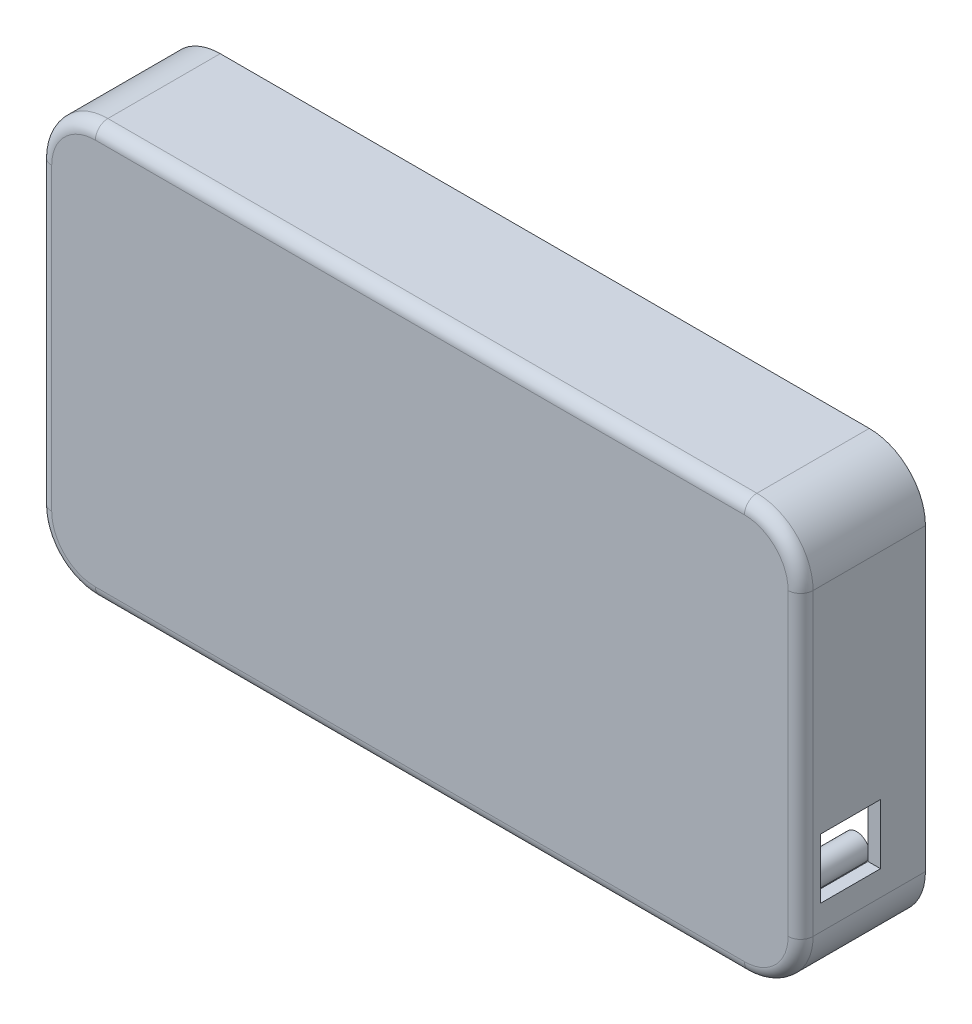
SolidWorks part; units mm, degrees
material "交联聚乙烯"
ref_plane "前视基准面" through (0, 0, 0) normal (0, 0, 1) x (1, 0, 0)
ref_plane "上视基准面" through (0, 0, 0) normal (0, 1, 0) x (1, 0, 0)
ref_plane "右视基准面" through (0, 0, 0) normal (1, 0, 0) x (0, 0, -1)
sketch "草图1" plane through (0, 0, 0) normal (0, 0, 1) x (1, 0, 0)
  line L1 (-130, 82.5) -> (130, 82.5)
  line L2 (-152.5, 60) -> (-152.5, -60)
  line L3 (-130, -82.5) -> (130, -82.5)
  line L4 (152.5, 60) -> (152.5, -60)
  line L5 (0, -82.5) -> (0, 82.5) construction
  line L6 (-152.5, 0) -> (152.5, 0) construction
  line L14 (-130, 77.5) -> (130, 77.5)
  line L15 (147.5, 60) -> (147.5, -60)
  line L16 (-130, -77.5) -> (130, -77.5)
  line L17 (-147.5, 60) -> (-147.5, -60)
  line L18 (-150.2, 60) -> (-150.2, -60)
  line L19 (-130, -80.2) -> (130, -80.2)
  line L20 (150.2, 60) -> (150.2, -60)
  line L21 (-130, 80.2) -> (130, 80.2)
  arc A0 (-130, -82.5) -> (-152.5, -60) centre (-130, -60) cw
  arc A1 (130, -82.5) -> (152.5, -60) centre (130, -60) ccw
  arc A2 (152.5, 60) -> (130, 82.5) centre (130, 60) ccw
  arc A3 (-152.5, 60) -> (-130, 82.5) centre (-130, 60) cw
  arc A12 (147.5, 60) -> (130, 77.5) centre (130, 60) ccw
  arc A13 (130, -77.5) -> (147.5, -60) centre (130, -60) ccw
  arc A14 (-130, -77.5) -> (-147.5, -60) centre (-130, -60) cw
  arc A15 (-147.5, 60) -> (-130, 77.5) centre (-130, 60) cw
  circle A16 centre (130, 60) radius 2.6
  circle A17 centre (130, 60) radius 5.1
  circle A18 centre (130, -60) radius 2.6
  circle A19 centre (130, -60) radius 5.1
  circle A20 centre (-130, 60) radius 2.6
  circle A21 centre (-130, 60) radius 5.1
  circle A22 centre (-130, -60) radius 2.6
  circle A23 centre (-130, -60) radius 5.1
  arc A24 (-130, -80.2) -> (-150.2, -60) centre (-130, -60) cw
  arc A25 (130, -80.2) -> (150.2, -60) centre (130, -60) ccw
  arc A26 (150.2, 60) -> (130, 80.2) centre (130, 60) ccw
  arc A27 (-150.2, 60) -> (-130, 80.2) centre (-130, 60) cw
  point P0 (0, 0)
  point P6 (-152.5, -82.5)
  point P9 (152.5, -82.5)
  point P12 (152.5, 82.5)
  dimension "D3" = 22.5
  dimension "D6" = 5.2
  dimension "D8" = 5.2
  dimension "D10" = 5.2
  dimension "D12" = 5.2
  dimension "D1" = 305
  dimension "D2" = 165
  dimension "D4" = 2.3
  dimension "D7" = 2.5
  dimension "D9" = 2.5
  dimension "D11" = 2.5
  dimension "D13" = 2.5
extrude "凸台-拉伸1" add sketch "草图1" along normal blind 50 contours A0 L2 A3 L1 A2 L4 A1 L3
extrude "切除-拉伸1" cut sketch "草图1<4>" along normal blind 45 contours A15 L17 A14 L16 A13 L15 A12 L14 region at (0, 0, 0)
sketch "草图1<4>" plane through (0, 0, 0) normal (0, 0, 1) x (1, 0, 0) same geometry as "草图1"
sketch "草图3" plane through (0, 0, 0) normal (0, 0, -1) x (-1, 0, 0)
extrude "切除-拉伸2" cut sketch "草图1<5>" along normal blind 5 contours A27 L21 A26 L20 A25 L19 A24 L18 L17 A15 L14 A12 L15 A13 L16 A14 region at (-144.0428, 74.0428, 0)
sketch "草图1<5>" plane through (0, 0, 0) normal (0, 0, 1) x (1, 0, 0) same geometry as "草图1"
extrude "切除-拉伸3" cut sketch "草图1<6>" along normal blind 5 contours A23 | A21 | A17 | A19
sketch "草图1<6>" plane through (0, 0, 0) normal (0, 0, 1) x (1, 0, 0) same geometry as "草图1"
extrude "切除-拉伸4" cut sketch "草图1<7>" along normal blind 25 contours A22 | A16 | A18 | A20 region at (130, 60, 0) region at (130, -60, 0) region at (-130, -60, 0)
sketch "草图1<7>" plane through (0, 0, 0) normal (0, 0, 1) x (1, 0, 0) same geometry as "草图1"
fillet "圆角2" radius 5 4 edges at (0, -82.5, 50) (152.5, 0, 50) (0, 82.5, 50) (-152.5, 0, 50) type face fillet first side face at (0, 0, 50) second side face at (-152.5, 0, 25) second side face at (0, -82.5, 25) second side face at (152.5, 0, 25) second side face at (0, 82.5, 25)
sketch3d "3D草图1"
  point P0 (44.0813, -82.5, 36.7135)
sketch "草图14" plane through (0, -82.5, 0) normal (0, -1, 0) x (1, 0, 0)
  line L0 (-130, 45) -> (130, 45) construction
  line L5 (-80, 38) -> (-71, 38) construction
  line L6 (-130, 45) -> (-130, 0) construction
  line L8 (-87, 33.5) -> (-73, 33.5)
  line L9 (-87, 33.5) -> (-87, 42.5)
  line L10 (-87, 42.5) -> (-73, 42.5)
  line L11 (-73, 33.5) -> (-73, 42.5)
  line L12 (-80, 42.5) -> (-80, 33.5) construction
  line L13 (-87, 38) -> (-73, 38) construction
  line L14 (-87, 33.5) -> (-73, 33.5)
  line L15 (-87, 42.5) -> (-73, 42.5)
  line L16 (0, 45) -> (0, 33.2265) construction
  circle A0 centre (-71, 38) radius 1.6
  circle A2 centre (-89, 38) radius 1.6
  point P0 (-80, 38)
  dimension "D5" = 3.2
  dimension "D1" = 14
  dimension "D2" = 9
  dimension "D3" = 7
  dimension "D4" = 9
  dimension "D6" = 50
extrude "USB口" cut sketch "草图14" against normal blind 5 contours L8 L11 L10 L9 | A2 | A0 region at (-80, -82.5, 38) region at (-89, -82.5, 38)
sketch "草图16" plane through (152.5, 0, 0) normal (1, 0, 0) x (0, 0, -1)
  line L0 (-45, 60) -> (-45, -60) construction
  line L3 (-42, -26) -> (-18, -26)
  line L4 (-42, -26) -> (-42, -50)
  line L5 (-42, -50) -> (-18, -50)
  line L6 (-18, -26) -> (-18, -50)
  line L7 (-30, -50) -> (-30, -26) construction
  line L8 (-42, -38) -> (-18, -38) construction
  line L9 (-45, -60) -> (0, -60) construction
  point P0 (-30, -38)
  dimension "D1" = 24
  dimension "D2" = 24
  dimension "D3" = 10
  dimension "D4" = 15
extrude "切除-拉伸12" cut sketch "草图16" against normal blind 5
sketch "草图18" plane through (-152.5, 0, 0) normal (-1, 0, 0) x (0, 0, 1)
  line L0 (45, -60) -> (45, 60) construction
  line L3 (45, -60) -> (0, -60) construction
  line L4 (18, -26) -> (42, -26)
  line L5 (18, -26) -> (18, -50)
  line L6 (18, -50) -> (42, -50)
  line L7 (42, -26) -> (42, -50)
  line L8 (30, -50) -> (30, -26) construction
  line L9 (18, -38) -> (42, -38) construction
  point P4 (30, -38)
  dimension "D1" = 24
  dimension "D2" = 24
  dimension "D3" = 10
  dimension "D4" = 15
extrude "切除-拉伸13" cut sketch "草图18" against normal blind 5
sketch "草图19" plane through (0, 0, 45) normal (0, 0, -1) x (-1, 0, 0)
  line L0 (-103, 36) -> (-18, 36) construction
  line L1 (-103, 40) -> (-18, 40)
  line L2 (-103, 32) -> (-18, 32)
  line L3 (152.5, 0) -> (-152.5, 0) construction
  line L4 (0, -82.5) -> (0, 82.5) construction
  line L5 (-147.5, 0) -> (-107.2295, 0) construction
  line L6 (0, 77.5) -> (0, 61.8371) construction
  line L7 (103, 36) -> (18, 36) construction
  line L8 (103, 40) -> (18, 40)
  line L9 (103, 32) -> (18, 32)
  line L10 (-103, -24) -> (-23, -24) construction
  line L11 (-103, -20) -> (-23, -20)
  line L12 (-103, -28) -> (-23, -28)
  line L14 (103, -24) -> (23, -24) construction
  line L15 (103, -20) -> (23, -20)
  line L16 (103, -28) -> (23, -28)
  arc A0 (-103, 40) -> (-103, 32) centre (-103, 36) ccw
  arc A1 (-18, 32) -> (-18, 40) centre (-18, 36) ccw
  arc A2 (103, 40) -> (103, 32) centre (103, 36) cw
  arc A3 (18, 32) -> (18, 40) centre (18, 36) cw
  arc A4 (-103, -20) -> (-103, -28) centre (-103, -24) ccw
  arc A5 (-23, -28) -> (-23, -20) centre (-23, -24) ccw
  arc A6 (103, -20) -> (103, -28) centre (103, -24) cw
  arc A7 (23, -28) -> (23, -20) centre (23, -24) cw
  point P2 (-60.5, 36)
  point P13 (60.5, 36)
  point P23 (-63, -24)
  point P33 (63, -24)
  dimension "D2" = 4
  dimension "D7" = 4
  dimension "D8" = 80
  dimension "D1" = 85
  dimension "D3" = 18
  dimension "D4" = 32
  dimension "D5" = 23
  dimension "D6" = 20
extrude "凸台-拉伸2" add sketch "草图19" along normal blind 40
sketch "草图29" plane through (0, 0, 45) normal (0, 0, -1) x (-1, 0, 0)
  line L0 (14.35, -45.2) -> (-14.35, -45.2)
  line L1 (12.85, -43.7) -> (-12.85, -43.7)
  line L2 (12.85, -43.7) -> (12.85, -20)
  line L3 (12.85, -20) -> (-12.85, -20)
  line L4 (-12.85, -43.7) -> (-12.85, -20)
  line L5 (0, -20) -> (0, -43.7) construction
  line L6 (12.85, -31.85) -> (-12.85, -31.85) construction
  line L7 (0, -41.7182) -> (0, 1.1541) construction
  line L8 (-14.35, -45.2) -> (-14.35, -18.5)
  line L9 (14.35, -18.5) -> (-14.35, -18.5)
  line L10 (17.8546, 0) -> (-23.7773, 0) construction
  line L11 (14.35, -45.2) -> (14.35, -18.5)
  line L12 (0, -31.85) -> (-17.5, -31.85) construction
  line L13 (12.85, -20) -> (12.85, -18.5)
  line L14 (-30, 20) -> (30, 20) construction
  line L15 (-30, 20) -> (-30, -10) construction
  line L16 (-30, -10) -> (30, -10) construction
  line L17 (30, 20) -> (30, -10) construction
  line L18 (0, -10) -> (0, 20) construction
  line L19 (-30, 5) -> (30, 5) construction
  line L20 (-12.85, -20) -> (-12.85, -18.5)
  circle A0 centre (-17.5, -31.85) radius 1.25
  circle A1 centre (-17.5, -31.85) radius 2.95
  circle A2 centre (17.5, -31.85) radius 1.25
  circle A3 centre (17.5, -31.85) radius 2.95
  circle A4 centre (-30, 20) radius 1.3
  circle A5 centre (30, 20) radius 1.3
  circle A6 centre (30, -10) radius 1.3
  circle A7 centre (-30, -10) radius 1.3
  circle A8 centre (-30, 20) radius 3.3
  circle A9 centre (30, 20) radius 3.3
  circle A10 centre (30, -10) radius 3.3
  circle A11 centre (-30, -10) radius 3.3
  point P0 (0, -31.85)
  point P21 (0, 0)
  dimension "D6" = 2.5
  dimension "D10" = 2.6
  dimension "D11" = 2.6
  dimension "D12" = 2.6
  dimension "D13" = 2.6
  dimension "D1" = 23.7
  dimension "D2" = 25.7
  dimension "D3" = 20
  dimension "D5" = 17.5
  dimension "D8" = 60
  dimension "D9" = 30
  dimension "D15" = 5
  dimension "D4" = 1.5
  dimension "D7" = 1.7
  dimension "D14" = 2
extrude "凸台-拉伸3" add sketch "草图29" along normal blind 2 contours L0 L11 L9 L8 L1 L4 L3 L2 region at (0, -44.808, 45)
extrude "凸台-拉伸4" add sketch "草图29<4>" along normal blind 5 contours A1 A0 | A3 A2 region at (20.3666, -31.85, 45) region at (-14.6334, -31.85, 45)
sketch "草图29<4>" plane through (0, 0, 45) normal (0, 0, -1) x (-1, 0, 0) same geometry as "草图29"
extrude "凸台-拉伸5" add sketch "草图29<5>" along normal blind 6.5 contours A8 A4 | A11 A7 | A9 A5 | A10 A6 region at (33.2067, 20, 45) region at (-26.7933, 20, 45) region at (-26.7933, -10, 45) region at (33.2067, -10, 45)
sketch "草图29<5>" plane through (0, 0, 45) normal (0, 0, -1) x (-1, 0, 0) same geometry as "草图29"
